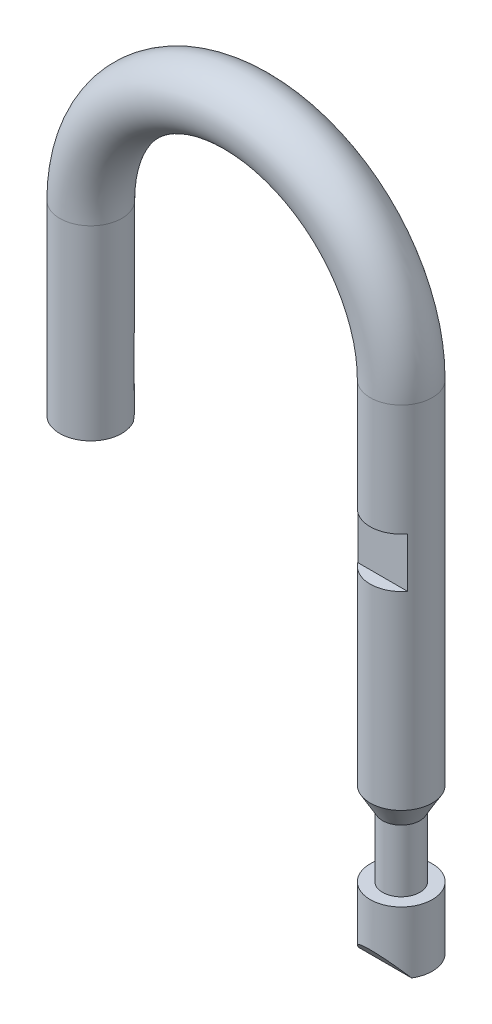
SolidWorks part; units mm, degrees
ref_plane "정면" through (0, 0, 0) normal (0, 0, 1) x (1, 0, 0)
ref_plane "윗면" through (0, 0, 0) normal (0, 1, 0) x (1, 0, 0)
ref_plane "우측면" through (0, 0, 0) normal (1, 0, 0) x (0, 0, -1)
sketch "스케치1" plane through (0, 0, 0) normal (0, 0, 1) x (1, 0, 0)
  line L0 (20, -7) -> (20, -10) construction
  line L1 (0, 0) -> (40, 0)
  line L2 (0, 0) -> (0, -40)
  line L3 (0, -40) -> (40, -40)
  line L4 (40, 0) -> (40, -40)
  line L5 (17, -10) -> (23, -10)
  line L6 (17, -10) -> (17, -31)
  line L7 (17, -31) -> (23, -31)
  line L8 (23, -10) -> (23, -31)
  line L9 (19, -10) -> (21, -10)
  line L10 (19, -10) -> (19, -7)
  line L11 (19, -7) -> (21, -7)
  line L12 (21, -10) -> (21, -7)
  line L13 (20, -10) -> (20, -40) construction
  line L14 (5, 5) -> (35, 5) construction
  line L15 (5, 5) -> (5, -10)
  line L16 (5, -10) -> (10, -10)
  line L17 (10, -10) -> (10, 5)
  line L18 (30, 5) -> (30, -35)
  line L19 (30, -35) -> (35, -35)
  line L20 (35, -35) -> (35, 5)
  line L22 (4, -4) -> (30, -4)
  line L23 (4, -4) -> (4, -8)
  line L24 (4, -8) -> (30, -8)
  line L25 (30, -4) -> (30, -8)
  line L26 (18, -4) -> (22, -4)
  line L27 (18, -4) -> (18, -9)
  line L28 (18, -9) -> (22, -9)
  line L29 (22, -4) -> (22, -9)
  arc A0 (10, 5) -> (30, 5) centre (20, 5) cw
  arc A1 (5, 5) -> (35, 5) centre (20, 5) cw
  point P30 (20, -9)
  point P31 (0, 0)
  point P32 (0, 0)
  point P33 (22, -8.5967)
  point P34 (30, -8)
  dimension "D7" = 5
  dimension "D8" = 10
  dimension "D1" = 2
  dimension "D2" = 3
  dimension "D3" = 21
  dimension "D4" = 6
  dimension "D5" = 40
  dimension "D6" = 40
  dimension "D9" = 40
  dimension "D10" = 15
  dimension "D11" = 10
  dimension "D12" = 5
  dimension "D13" = 4
  dimension "D14" = 4
  dimension "D15" = 5
  dimension "D16" = 2
  dimension "D17" = 1
sketch "스케치2" plane through (0, 0, 0) normal (0, 0, 1) x (1, 0, 0)
  line L0 (5, 5) -> (35, 5) construction
  line L1 (7.5, 5) -> (7.5, -10)
  line L4 (32.5, 5) -> (32.5, -35)
  line L7 (30, -35) -> (35, -35) construction
  line L8 (5, -10) -> (10, -10) construction
  arc A0 (7.5, 5) -> (32.5, 5) centre (20, 5) cw
  arc A1 (30, 5) -> (10, 5) centre (20, 5) ccw construction
  dimension "D1" = 2.5
sketch "스케치3" plane through (0, 0, 0) normal (0, 1, 0) x (1, 0, 0)
  circle A0 centre (7.5, 0) radius 2.5
  point P2 (0, 0)
  dimension "D1" = 5
sweep "스윕1" add profiles "스케치3" path "스케치2"
sketch "스케치4" plane through (0, 0, 0) normal (1, 0, 0) x (0, 0, -1)
  line L0 (9.0129, -4) -> (1.5, -4)
  line L1 (1.5, -4) -> (1.5, -8)
  line L2 (1.5, -8) -> (9.0129, -8)
  line L3 (9.0129, -8) -> (9.0129, -4)
  line L4 (1.3, -10) -> (2.5, -10)
  line L5 (-1.5, -4) -> (-10.8743, -4)
  line L6 (-1.5, -4) -> (-1.5, -8)
  line L7 (-1.5, -8) -> (-10.8743, -8)
  line L8 (-10.8743, -4) -> (-10.8743, -8)
  line L9 (2.5, -10) -> (2.5, -8.5)
  line L10 (2.5, -8.5) -> (1.3, -10)
  line L11 (2.5, -10) -> (2.5, 5) construction
  line L12 (-2.5, -10) -> (2.5, -10) construction
  line L13 (-2.5, -35) -> (-2.5, -33.5)
  line L14 (-2.5, 5) -> (-2.5, -35) construction
  line L15 (-2.5, -33.5) -> (-1.3, -35)
  line L16 (-2.5, -35) -> (2.5, -35) construction
  line L17 (-1.3, -35) -> (-2.5, -35)
  point P25 (-1.5, -16.1046)
  dimension "D1" = 1.5
  dimension "D2" = 1.5
  dimension "D3" = 0.5
  dimension "D4" = 0.2
extrude "컷-돌출1" cut sketch "스케치4" along normal blind 10 contours L2 L3 L0 L1 | L9 L10 L4 region at (0, -6, -5.2564) region at (0, -9.5, -2.1)
extrude "컷-돌출2" cut sketch "스케치4<3>" along normal through all from offset 10 contours L5 L8 L7 L6 | L17 L15 L13
sketch "스케치4<3>" plane through (0, 0, 0) normal (1, 0, 0) x (0, 0, -1) same geometry as "스케치4"
sketch "스케치5" plane through (0, -35, 0) normal (0, -1, 0) x (1, 0, 0)
  circle A0 centre (32.5, 0) radius 2.5
  circle A1 centre (32.5, 0) radius 1.5
  dimension "D1" = 3
  dimension "D2" = 5
extrude "컷-돌출3" cut sketch "스케치5" against normal blind 5 from offset 5 offset against normal yes
chamfer "모따기1" distance 1 angle 60 1 edges at (35, -25, 0) first distance on face at (34, -25, 0)
